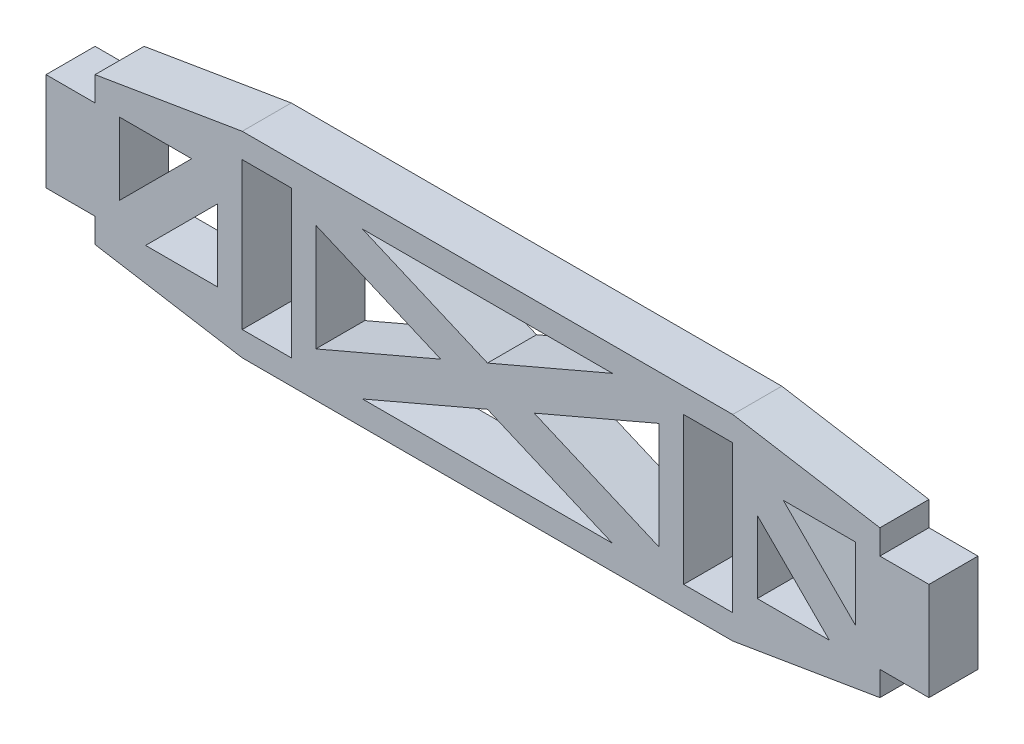
SolidWorks part; units mm, degrees
material "PE High Density"
ref_plane "Front Plane" through (0, 0, 0) normal (0, 0, 1) x (1, 0, 0)
ref_plane "Top Plane" through (0, 0, 0) normal (0, 1, 0) x (1, 0, 0)
ref_plane "Right Plane" through (0, 0, 0) normal (1, 0, 0) x (0, 0, -1)
sketch "Sketch1" plane through (0, 0, 0) normal (0, 0, 1) x (1, 0, 0)
  line L0 (-50.8, -6.35) -> (-50.8, 6.35) construction
  line L1 (-50.8, -9.525) -> (50.8, -9.525) construction
  line L2 (-50.8, -9.525) -> (-50.8, -6.35)
  line L3 (-50.8, 9.525) -> (50.8, 9.525) construction
  line L4 (50.8, -9.525) -> (50.8, -6.35)
  line L5 (-50.8, -9.525) -> (50.8, 9.525) construction
  line L6 (-50.8, 9.525) -> (50.8, -9.525) construction
  line L7 (-50.8, 6.35) -> (-57.15, 6.35)
  line L8 (-50.8, 6.35) -> (-50.8, -6.35) construction
  line L9 (-50.8, -6.35) -> (-57.15, -6.35)
  line L10 (-57.15, 6.35) -> (-57.15, -6.35)
  line L11 (50.8, 6.35) -> (57.15, 6.35)
  line L12 (50.8, 6.35) -> (50.8, -6.35) construction
  line L13 (50.8, -6.35) -> (57.15, -6.35)
  line L14 (57.15, 6.35) -> (57.15, -6.35)
  line L15 (-50.8, 6.35) -> (-50.8, 9.525)
  line L16 (50.8, -6.35) -> (50.8, 6.35) construction
  line L17 (50.8, 6.35) -> (50.8, 9.525)
  line L18 (0, -3.4925) -> (0, 3.4925) construction
  line L19 (-31.75, 9.525) -> (-25.4, 9.525)
  line L20 (-31.75, 9.525) -> (-31.75, -9.525)
  line L21 (-31.75, -9.525) -> (-25.4, -9.525)
  line L22 (-25.4, 9.525) -> (-25.4, -9.525)
  line L23 (31.75, -9.525) -> (25.4, -9.525)
  line L24 (25.4, 9.525) -> (25.4, -9.525)
  line L25 (31.75, 9.525) -> (25.4, 9.525)
  line L26 (31.75, 9.525) -> (31.75, -9.525)
  line L27 (-50.8, 9.525) -> (-31.75, 12.7)
  line L28 (-31.75, 12.7) -> (31.75, 12.7)
  line L29 (31.75, 12.7) -> (50.8, 9.525)
  line L30 (50.8, -9.525) -> (31.75, -12.7)
  line L31 (31.75, -12.7) -> (-31.75, -12.7)
  line L32 (-31.75, -12.7) -> (-50.8, -9.525)
  point P0 (0, 0)
  point P15 (57.15, 0)
  point P16 (-57.15, 0)
  point P26 (-31.75, 0)
  dimension "D1" = 101.6
  dimension "D2" = 6.35
  dimension "D3" = 12.7
  dimension "D4" = 3.175
  dimension "D5" = 50.8
  dimension "D6" = 19.05
  dimension "D7" = 3.175
extrude "Boss-Extrude1" add sketch "Sketch1" along normal mid plane 6.35
sketch "Sketch2" plane through (0, 0, 3.175) normal (0, 0, 1) x (1, 0, 0)
  line L0 (-1000, 0) -> (49000, 0) construction
  line L1 (-47.625, 6.35) -> (-47.625, -6.35)
  line L2 (-47.625, -6.35) -> (-34.925, -6.35)
  line L3 (-34.925, -6.35) -> (-34.925, 6.35)
  line L4 (-34.925, 6.35) -> (-47.625, 6.35)
  line L5 (-50.8, 6.35) -> (-57.15, 6.35) construction
  line L6 (-50.8, 9.525) -> (-50.8, 6.35) construction
  line L7 (-38.2926, 6.35) -> (-47.625, -2.9824)
  line L8 (-50.8, 6.35) -> (-47.625, 6.35) construction
  line L9 (22.225, -9.525) -> (-22.225, -9.525)
  line L10 (22.225, -9.525) -> (22.225, 9.525)
  line L11 (22.225, 9.525) -> (-22.225, 9.525)
  line L12 (-22.225, -9.525) -> (-22.225, 9.525)
  line L13 (22.225, -9.525) -> (-22.225, 9.525) construction
  line L14 (22.225, 9.525) -> (-22.225, -9.525) construction
  line L15 (-34.925, 6.35) -> (-31.75, 6.35) construction
  line L16 (-25.4, 9.525) -> (-22.225, 9.525) construction
  line L17 (22.225, 9.525) -> (25.4, 9.525) construction
  line L18 (-47.625, 6.35) -> (-34.925, -6.35) construction
  line L19 (-34.925, 6.35) -> (-47.625, -6.35) construction
  line L20 (-34.925, 2.9824) -> (-44.2574, -6.35)
  line L21 (-36.6088, 8.0338) -> (-49.3088, -4.6662) construction
  line L22 (-33.2412, 4.6662) -> (-45.9412, -8.0338) construction
  line L23 (22.225, -6.9343) -> (-16.18, 9.525)
  line L24 (16.18, 9.525) -> (-22.225, -6.9343)
  line L25 (16.18, -9.525) -> (-22.225, 6.9343)
  line L26 (22.225, 6.9343) -> (-16.18, -9.525)
  line L27 (23.163, -7.3363) -> (-21.287, 11.7137) construction
  line L28 (21.287, -11.7137) -> (-23.163, 7.3363) construction
  line L29 (21.287, 11.7137) -> (-23.163, -7.3363) construction
  line L30 (23.163, 7.3363) -> (-21.287, -11.7137) construction
  line L31 (0, -3.4925) -> (0, 3.4925) construction
  line L32 (38.2926, 6.35) -> (47.625, -2.9824)
  line L33 (34.925, 2.9824) -> (44.2574, -6.35)
  line L34 (34.925, -6.35) -> (34.925, 6.35)
  line L35 (47.625, -6.35) -> (34.925, -6.35)
  line L36 (47.625, 6.35) -> (47.625, -6.35)
  line L37 (34.925, 6.35) -> (47.625, 6.35)
  line L38 (-25.4, -9.525) -> (-25.4, 9.525) construction
  line L39 (-31.75, 9.525) -> (-31.75, -9.525) construction
  point P9 (-47.625, 0)
  point P14 (0, 0)
  dimension "D1" = 3.175
  dimension "D6" = 19.05
  dimension "D2" = 2.3813
  dimension "D3" = 2.3813
  dimension "D4" = 2.3813
  dimension "D5" = 2.3813
extrude "Cut-Extrude1" cut sketch "Sketch2" against normal through all contours L7 L4 L1 | L3 L20 L2 | L24 L25 L12 | L24 L11 L23 | L10 L26 L23 | L25 L26 L9 | L35 L33 L34 | L37 L32 L36 region at (-44.5142, 3.2392, 3.175) region at (-38.0358, -3.2392, 3.175) region at (0, -7.2136, 3.175) region at (16.8317, 0, 3.175) region at (-16.8317, 0, 3.175) region at (0, 7.2136, 3.175) region at (44.5142, 3.2392, 3.175) region at (38.0358, -3.2392, 3.175)
equation "\"D2@Sketch2\"=\"D3@Sketch2\""
equation "\"D5@Sketch2\"=\"D3@Sketch2\""
equation "\"D4@Sketch2\"=\"D5@Sketch2\""
